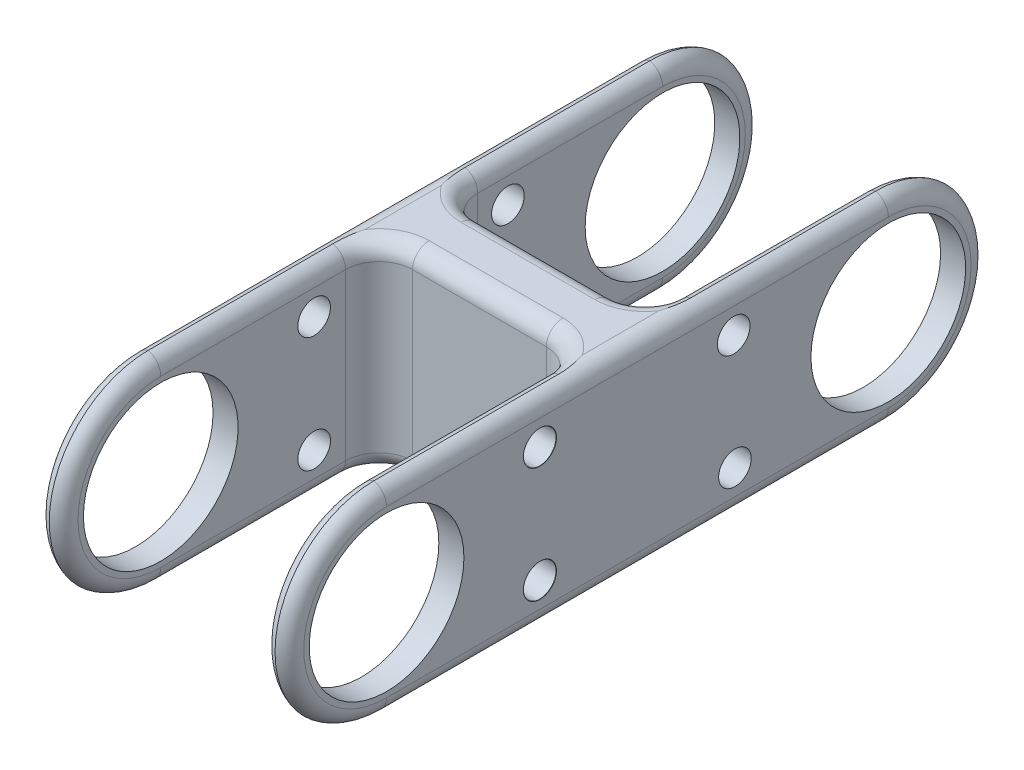
SolidWorks part; units mm, degrees
ref_plane "Front Plane" through (0, 0, 0) normal (0, 0, 1) x (1, 0, 0)
ref_plane "Top Plane" through (0, 0, 0) normal (0, 1, 0) x (1, 0, 0)
ref_plane "Right Plane" through (0, 0, 0) normal (1, 0, 0) x (0, 0, -1)
sketch "Sketch1" plane through (0, 0, 0) normal (1, 0, 0) x (0, 0, -1)
  line L0 (0, 11.9) -> (60, 11.9)
  line L1 (0, -11.9) -> (60, -11.9)
  line L2 (30, 11.9) -> (30, -11.9) construction
  circle A0 centre (0, 0) radius 9.25
  arc A1 (0, 11.9) -> (0, -11.9) centre (0, 0) ccw
  circle A2 centre (60, 0) radius 9.25
  arc A3 (60, 11.9) -> (60, -11.9) centre (60, 0) cw
  dimension "D1" = 18.5
  dimension "D2" = 23.8
  dimension "D3" = 60
extrude "Boss-Extrude1" add sketch "Sketch1" along normal blind 30
sketch "Sketch2" plane through (0, 11.9, 0) normal (0, 1, 0) x (1, 0, 0)
  line L0 (0, -11.9) -> (30, -11.9) construction
  line L1 (3, -11.9) -> (27, -11.9)
  line L2 (3, -11.9) -> (3, 26.1)
  line L3 (3, 26.1) -> (27, 26.1)
  line L4 (27, -11.9) -> (27, 26.1)
  line L5 (0, 30) -> (30, 30) construction
  line L6 (0, 60) -> (0, 0) construction
  line L7 (30, 60) -> (30, 0) construction
  line L8 (3, 33.9) -> (27, 33.9)
  line L9 (27, 71.9) -> (27, 33.9)
  line L10 (3, 71.9) -> (27, 71.9)
  line L11 (3, 71.9) -> (3, 33.9)
  dimension "D1" = 38
  dimension "D2" = 3
  dimension "D3" = 3
extrude "Cut-Extrude1" cut sketch "Sketch2" against normal through all
ref_plane "Plane1" through (0, 0, -30) normal (0, 0, 1) x (1, 0, 0)
fillet "Fillet1" radius 4 4 edges at (27, 0, -26.1) (3, 0, -26.1) (27, 0, -33.9) (3, 0, -33.9)
hole_wizard "M3.5 Clearance Hole1" positions "Sketch3" profile "Sketch4" hole size "M3.5" standard "ANSI Metric" end condition through all
sketch "Sketch3" plane through (0, 0, 0) normal (-1, 0, 0) x (0, 0, 1)
  circle A0 centre (-41.511, 6.9) radius 1.7024 construction
  point P0 (-41.66, -6.9)
  point P3 (-41.511, 6.9)
sketch "Sketch4" plane through (0, -6.9, -41.66) normal (0, 1, 0) x (0, 0, 1)
  line L0 (0, 0) -> (0, 30)
  line L1 (0, 30) -> (1.95, 30)
  line L2 (1.95, 30) -> (1.95, 0.025)
  line L3 (1.95, 0.025) -> (1.975, 0)
  line L5 (1.975, 0) -> (0, 0)
  line L6 (-1.95, 0.025) -> (-1.975, 0) construction
  line L11 (0, -6.35) -> (0, 107.95) construction
  dimension "Thru Hole Dia." = 3.9
  dimension "Thru Hole Depth" = 30
  dimension "Near C'Sink Dia." = 3.95
  dimension "Near C'Sink Angle" = 90
sketch "Sketch5" plane through (0, 0, -33.9) normal (0, 0, -1) x (-1, 0, 0)
  line L0 (-23, 11.9) -> (-23, -11.9) construction
  line L1 (-23, 0) -> (-7, 0) construction
  line L2 (-7, -11.9) -> (-7, 11.9) construction
  line B0 (-23, -3.65) -> (-23, -10.15)
  line B1 (-23, -3.65) -> (-20, -3.65)
  line B2 (-20, -3.65) -> (-20, -10.15)
  line B3 (-23, -10.15) -> (-20, -10.15)
  line B4 (-23, 0) -> (-7, 0) construction
  line B5 (-14.9675, -0.1255) -> (-15, -8.8352) construction
  line B6 (-7.01, -10.2096) -> (-10.0099, -10.1872)
  line B7 (-9.9615, -3.6874) -> (-10.0099, -10.1872)
  line B8 (-6.9616, -3.7098) -> (-9.9615, -3.6874)
  line B9 (-6.9616, -3.7098) -> (-7.01, -10.2096)
  line B10 (-6.9616, 3.7098) -> (-7.01, 10.2096)
  line B11 (-6.9616, 3.7098) -> (-9.9615, 3.6874)
  line B12 (-9.9615, 3.6874) -> (-10.0099, 10.1872)
  line B13 (-7.01, 10.2096) -> (-10.0099, 10.1872)
  line B14 (-23, 10.15) -> (-20, 10.15)
  line B15 (-20, 3.65) -> (-20, 10.15)
  line B16 (-23, 3.65) -> (-20, 3.65)
  line B17 (-23, 3.65) -> (-23, 10.15)
sketch_block_instance "Block1-1"
sketch_block "Block1" parameters "D1"=3, "D2"=6.5
sketch "Sketch6" plane through (30, 0, 0) normal (-1, 0, 0) x (0, 0, 1)
  line L0 (-39.685, -6.9) -> (-43.635, -6.9) construction
  circle A0 centre (-41.66, -6.9) radius 1.975 construction
hole_wizard "M3.5 Clearance Hole2" positions "Sketch9" profile "Sketch8" hole size "M3.5" standard "ANSI Metric" end condition through all
sketch "Sketch9" plane through (30, 0, 0) normal (1, 0, 0) x (0, 0, -1)
  point P0 (18.34, 6.9)
  point P3 (18.34, -6.9)
sketch "Sketch8" plane through (30, 6.9, -18.34) normal (0, 1, 0) x (0, 0, -1)
  line L0 (0, 0) -> (0, 30)
  line L1 (0, 30) -> (1.95, 30)
  line L2 (1.95, 30) -> (1.95, 0.025)
  line L3 (1.95, 0.025) -> (1.975, 0)
  line L5 (1.975, 0) -> (0, 0)
  line L6 (-1.95, 0.025) -> (-1.975, 0) construction
  line L11 (0, -6.35) -> (0, 107.95) construction
  dimension "Thru Hole Dia." = 3.9
  dimension "Thru Hole Depth" = 30
  dimension "Near C'Sink Dia." = 3.95
  dimension "Near C'Sink Angle" = 90
sketch "Sketch10" plane through (0, 0, -26.1) normal (0, 0, 1) x (1, 0, 0)
  line L0 (-1.0691, -12.5585) -> (14.9309, -12.5585) construction
  line L1 (23, 0) -> (7, 0) construction
  line L2 (23, -11.9) -> (23, 11.9) construction
  line L3 (7, 11.9) -> (7, -11.9) construction
  line B0 (7, -3.65) -> (7, -10.15)
  line B1 (7, -3.65) -> (10, -3.65)
  line B2 (10, -3.65) -> (10, -10.15)
  line B3 (7, -10.15) -> (10, -10.15)
  line B4 (22.99, -10.2096) -> (19.9901, -10.1872)
  line B5 (20.0385, -3.6874) -> (19.9901, -10.1872)
  line B6 (23.0384, -3.7098) -> (20.0385, -3.6874)
  line B7 (23.0384, -3.7098) -> (22.99, -10.2096)
  line B8 (23.0384, 3.7098) -> (22.99, 10.2096)
  line B9 (23.0384, 3.7098) -> (20.0385, 3.6874)
  line B10 (20.0385, 3.6874) -> (19.9901, 10.1872)
  line B11 (22.99, 10.2096) -> (19.9901, 10.1872)
  line B12 (7, 10.15) -> (10, 10.15)
  line B13 (10, 3.65) -> (10, 10.15)
  line B14 (7, 3.65) -> (10, 3.65)
  line B15 (7, 3.65) -> (7, 10.15)
sketch_block_instance "Block1-2"
fillet "Fillet2" [suppressed] radius 2
hole_wizard "M3.5 Clearance Hole3" positions "Sketch11" profile "Sketch12" hole size "M3.5" standard "ANSI Metric" end condition through all
sketch "Sketch11" plane through (30, 0, 0) normal (1, 0, 0) x (0, 0, -1)
  point P0 (18.34, 6.9)
  point P3 (18.34, -6.9)
sketch "Sketch12" plane through (30, 6.9, -18.34) normal (0, 1, 0) x (0, 0, -1)
  line L0 (0, 0) -> (0, 30)
  line L1 (0, 30) -> (1.95, 30)
  line L2 (1.95, 30) -> (1.95, 0.025)
  line L3 (1.95, 0.025) -> (1.975, 0)
  line L5 (1.975, 0) -> (0, 0)
  line L6 (-1.95, 0.025) -> (-1.975, 0) construction
  line L11 (0, -6.35) -> (0, 107.95) construction
  dimension "Thru Hole Dia." = 3.9
  dimension "Thru Hole Depth" = 30
  dimension "Near C'Sink Dia." = 3.95
  dimension "Near C'Sink Angle" = 90
sketch "Sketch13" [suppressed] plane through (0, 0, 0) normal (-1, 0, 0) x (0, 0, 1)
  line L0 (-125.6084, 9.9) -> (-125.6084, -9.9) construction
  line L1 (0, 9.9) -> (-60, 9.9) construction
  line L2 (-60, -9.9) -> (0, -9.9) construction
  point P0 (-128.6084, 6.9)
  dimension "D1" = 3
fillet "Fillet3" radius 2 32 edges at (0, 0, -71.9) (0, -11.9, -30) (0, 0, 11.9) (3, 0, -71.9) (3, -11.9, -48.95) (4.1716, -11.9, -35.0716) (15, -11.9, -33.9) (25.8284, -11.9, -35.0716) (27, -11.9, -48.95) (27, 0, -71.9) (30, 0, -71.9) (30, -11.9, -30) (30, 0, 11.9) (27, 0, 11.9) (27, -11.9, -11.05) (25.8284, -11.9, -24.9284) (15, -11.9, -26.1) (4.1716, -11.9, -24.9284) (3, -11.9, -11.05) (3, 0, 11.9) (0, 11.9, -30) (3, 11.9, -48.95) (4.1716, 11.9, -35.0716) (15, 11.9, -33.9) (25.8284, 11.9, -35.0716) (27, 11.9, -48.95) (30, 11.9, -30) (27, 11.9, -11.05) (25.8284, 11.9, -24.9284) (15, 11.9, -26.1) (4.1716, 11.9, -24.9284) (3, 11.9, -11.05)
